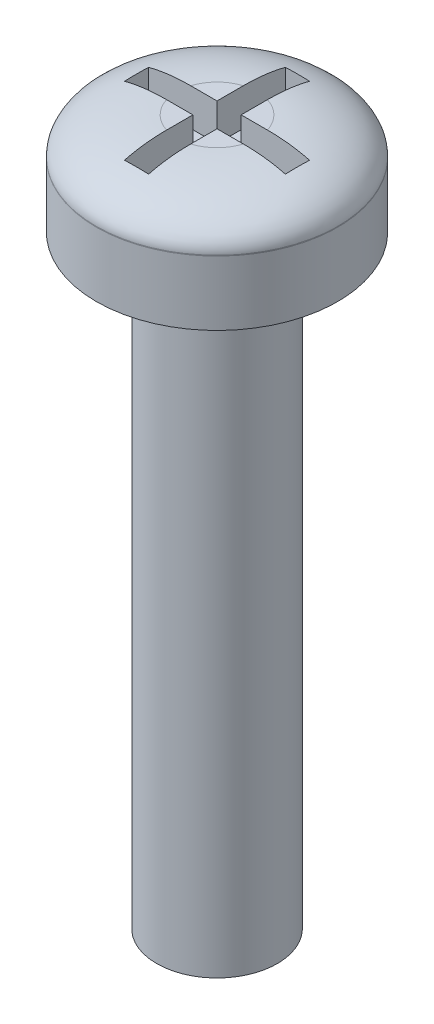
SolidWorks part; units mm, degrees
ref_plane "Přední rovina" through (0, 0, 0) normal (0, 0, 1) x (1, 0, 0)
ref_plane "Horní rovina" through (0, 0, 0) normal (0, 1, 0) x (1, 0, 0)
ref_plane "Pravá rovina" through (0, 0, 0) normal (1, 0, 0) x (0, 0, -1)
sketch "Skica1" plane through (0, 0, 0) normal (0, 1, 0) x (1, 0, 0)
  circle A0 centre (0, 0) radius 1.5
  dimension "D1" = 3
extrude "Přidat vysunutím1" add sketch "Skica1" along normal blind 15
sketch "Skica2" plane through (0, 15, 0) normal (0, 1, 0) x (1, 0, 0)
  circle A0 centre (0, 0) radius 3
  dimension "D1" = 6
extrude "Přidat vysunutím2" add sketch "Skica2" along normal blind 1.6
sketch "Skica3" plane through (0, 16.6, 0) normal (0, 1, 0) x (1, 0, 0)
  circle A0 centre (0, 0) radius 2.9999
extrude "Přidat vysunutím3" add sketch "Skica3" along normal blind 0.92
fillet "Zaoblit1" radius 0.9 1 edges at (0, 17.52, 2.9999) second distance 2 first distance on face at (0, 17.52, 2.9999)
sketch "Skica4" plane through (0, 17.52, 0) normal (0, 1, 0) x (1, 0, 0)
  line L1 (-0.3, 2) -> (0.3, 2)
  line L2 (-0.3, 2) -> (-0.3, -2)
  line L3 (-0.3, -2) -> (0.3, -2)
  line L4 (0.3, 2) -> (0.3, -2)
  line L5 (-0.3, 2) -> (0.3, -2) construction
  line L6 (-0.3, -2) -> (0.3, 2) construction
  line L7 (-2, 0.3) -> (2, 0.3)
  line L8 (-2, 0.3) -> (-2, -0.3)
  line L9 (-2, -0.3) -> (2, -0.3)
  line L10 (2, 0.3) -> (2, -0.3)
  line L11 (-2, 0.3) -> (2, -0.3) construction
  line L12 (-2, -0.3) -> (2, 0.3) construction
  point P0 (0, 0)
  point P6 (0, 0)
  dimension "D1" = 4
  dimension "D2" = 0.6
extrude "Odebrat vysunutím1" cut sketch "Skica4" against normal blind 0.92 contours L4 L2 L3 | L9 L2 L4 | L2 L9 L4 L7 | L9 L2 L7 | L8 L9 L7 | L2 L7 L4 | L4 L1 L2 | L4 L9 L7 | L10 L7 L9 region at (0, 17.52, -1.15) region at (0, 17.52, 0) region at (-1.15, 17.52, 0) region at (1.15, 17.52, 0) region at (0, 17.52, 1.15)
